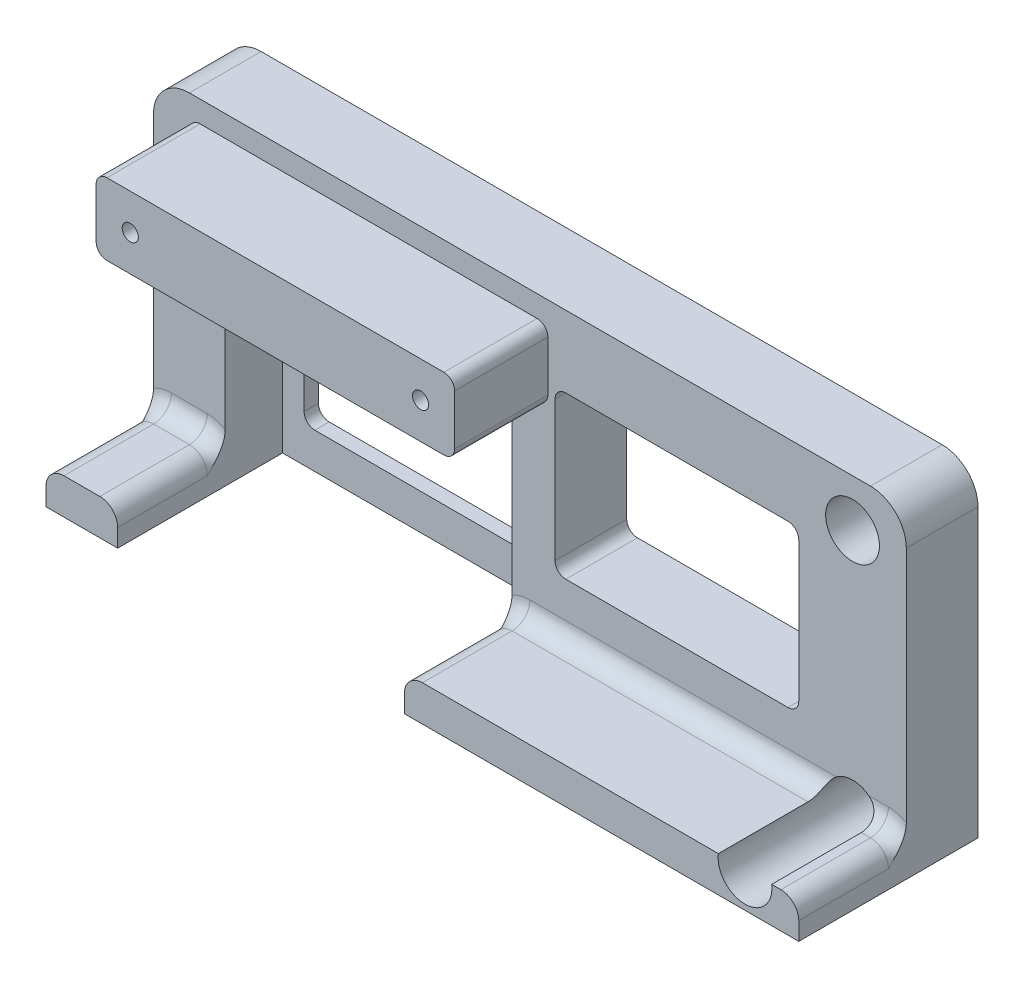
SolidWorks part; units mm, degrees
ref_plane "Front Plane" through (0, 0, 0) normal (0, 0, 1) x (1, 0, 0)
ref_plane "Top Plane" through (0, 0, 0) normal (0, 1, 0) x (1, 0, 0)
ref_plane "Right Plane" through (0, 0, 0) normal (1, 0, 0) x (0, 0, -1)
sketch "Sketch1" plane through (0, 0, 0) normal (0, 0, 1) x (1, 0, 0)
  line L1 (0, 0) -> (210, 0)
  line L2 (0, 0) -> (0, -90)
  line L3 (0, -90) -> (210, -90)
  line L4 (210, 0) -> (210, -90)
  dimension "D1" = 90
  dimension "D2" = 210
extrude "Boss-Extrude1" add sketch "Sketch1" along normal blind 20
sketch "Sketch2" plane through (0, 0, 20) normal (0, 0, 1) x (1, 0, 0)
  line L0 (0, -90) -> (210, -90) construction
  line L1 (210, -90) -> (210, 0) construction
  circle A0 centre (195, -13.2) radius 1.6
  circle A1 centre (195, -81) radius 1.6
  dimension "D1" = 3.2
  dimension "D2" = 3.2
  dimension "D3" = 9
  dimension "D4" = 15
  dimension "D5" = 15
  dimension "D6" = 67.8
extrude "Cut-Extrude1" cut sketch "Sketch2" against normal blind 20
sketch "Sketch3" plane through (0, 0, 20) normal (0, 0, 1) x (1, 0, 0)
  line L0 (0, -90) -> (210, -90) construction
  line L1 (210, -90) -> (100, -90)
  line L2 (210, -90) -> (210, -80)
  line L3 (210, -80) -> (100, -80)
  line L4 (100, -90) -> (100, -80)
  line L5 (210, -90) -> (210, 0) construction
  dimension "D1" = 10
  dimension "D2" = 0
  dimension "D5" = 110
extrude "Boss-Extrude2" add sketch "Sketch3" along normal blind 30
sketch "Sketch4" plane through (0, 0, 20) normal (0, 0, 1) x (1, 0, 0)
  line L0 (0, 0) -> (0, -90) construction
  line L1 (10, -6) -> (110, -6)
  line L2 (10, -6) -> (10, -26)
  line L3 (10, -26) -> (110, -26)
  line L4 (110, -6) -> (110, -26)
  line L5 (0, -90) -> (100, -90) construction
  dimension "D1" = 20
  dimension "D2" = 100
  dimension "D3" = 10
  dimension "D4" = 64
extrude "Boss-Extrude3" add sketch "Sketch4" along normal blind 26
sketch "Sketch5" plane through (0, 0, 46) normal (0, 0, 1) x (1, 0, 0)
  line L0 (10, -6) -> (10, -26) construction
  line L2 (110, -26) -> (110, -6) construction
  circle A0 centre (100.5, -16) radius 2.25
  circle A1 centre (19.5, -16) radius 2.25
  point P6 (10, -16)
  point P9 (110, -16)
  dimension "D1" = 4.5
  dimension "D2" = 4.5
  dimension "D5" = 81
  dimension "D6" = 9.5
extrude "Cut-Extrude2" cut sketch "Sketch5" against normal through all
sketch "Sketch7" plane through (0, 0, 20) normal (0, 0, 1) x (1, 0, 0)
  line L0 (10, -26) -> (110, -26) construction
  line L1 (20, -26) -> (100, -26)
  line L2 (20, -26) -> (20, -90)
  line L3 (20, -90) -> (100, -90)
  line L4 (100, -26) -> (100, -90)
  line L5 (0, -90) -> (100, -90) construction
  line L6 (0, 0) -> (0, -90) construction
  line L7 (100, -80) -> (100, -90) construction
  dimension "D1" = 20
  dimension "D2" = 0
extrude "Cut-Extrude3" cut sketch "Sketch7" against normal blind 16
sketch "Sketch8" plane through (0, 0, 20) normal (0, 0, 1) x (1, 0, 0)
  circle A0 centre (195, -13.2) radius 7.5
  dimension "D1" = 15
extrude "Cut-Extrude4" cut sketch "Sketch8" against normal blind 12
sketch "Sketch9" plane through (0, 0, 50) normal (0, 0, 1) x (1, 0, 0)
  circle A0 centre (195, -81) radius 7.5
  dimension "D1" = 15
extrude "Cut-Extrude5" cut sketch "Sketch9" against normal blind 42
sketch "Sketch10" plane through (0, 0, 20) normal (0, 0, 1) x (1, 0, 0)
  line L0 (210, 0) -> (0, 0) construction
  line L1 (112, -20) -> (180, -20)
  line L2 (112, -20) -> (112, -65)
  line L3 (112, -65) -> (180, -65)
  line L4 (180, -20) -> (180, -65)
  line L5 (210, -80) -> (210, 0) construction
  line L6 (0, -90) -> (210, -90) construction
  line L7 (100, -80) -> (100, -26) construction
  point P12 (100, -53)
  dimension "D1" = 20
  dimension "D2" = 30
  dimension "D3" = 25
  dimension "D4" = 12
extrude "Cut-Extrude6" cut sketch "Sketch10" against normal blind 46
sketch "Sketch11" plane through (0, 0, 20) normal (0, 0, 1) x (1, 0, 0)
  line L0 (20, -26) -> (20, -90) construction
  line L1 (0, -90) -> (20, -90)
  line L2 (0, -90) -> (0, -80)
  line L3 (0, -80) -> (20, -80)
  line L4 (20, -90) -> (20, -80)
  dimension "D1" = 10
extrude "Boss-Extrude5" add sketch "Sketch11" along normal blind 30
fillet "Fillet1" radius 10 2 edges at (0, 0, 10) (210, 0, 10)
sketch "Sketch12" plane through (0, 0, 4) normal (0, 0, 1) x (1, 0, 0)
  line L0 (100, -26) -> (20, -26) construction
  line L1 (26, -34) -> (94, -34)
  line L2 (26, -34) -> (26, -80)
  line L3 (26, -80) -> (94, -80)
  line L4 (94, -34) -> (94, -80)
  line L5 (20, -90) -> (100, -90) construction
  line L6 (20, -26) -> (20, -90) construction
  line L7 (100, -90) -> (100, -26) construction
  dimension "D1" = 8
  dimension "D2" = 10
  dimension "D3" = 6
  dimension "D4" = 6
extrude "Cut-Extrude7" cut sketch "Sketch12" against normal blind 30
fillet "Fillet2" radius 5 4 edges at (210, -80, 35) (100, -80, 35) (20, -80, 35) (0, -80, 35)
fillet "Fillet3" radius 5 7 edges at (101.4645, -81.4645, 20) (18.5355, -81.4645, 20) (1.4645, -81.4645, 20) (146.2835, -80, 20) (10, -80, 20) (208.5355, -81.4645, 20) (203.7165, -80, 20)
fillet "Fillet4" radius 3 10 edges at (94, -80, 2) (26, -80, 2) (26, -34, 2) (94, -34, 2) (180, -65, 10) (112, -65, 10) (112, -20, 10) (180, -20, 10) (20, -26, 12) (100, -26, 12)
fillet "Fillet5" radius 3 4 edges at (110, -26, 33) (110, -6, 33) (10, -26, 33) (10, -6, 33)
equation "\"D6@Sketch5\"=\"D2@Sketch4\"/2-\"D5@Sketch5\"/2"
